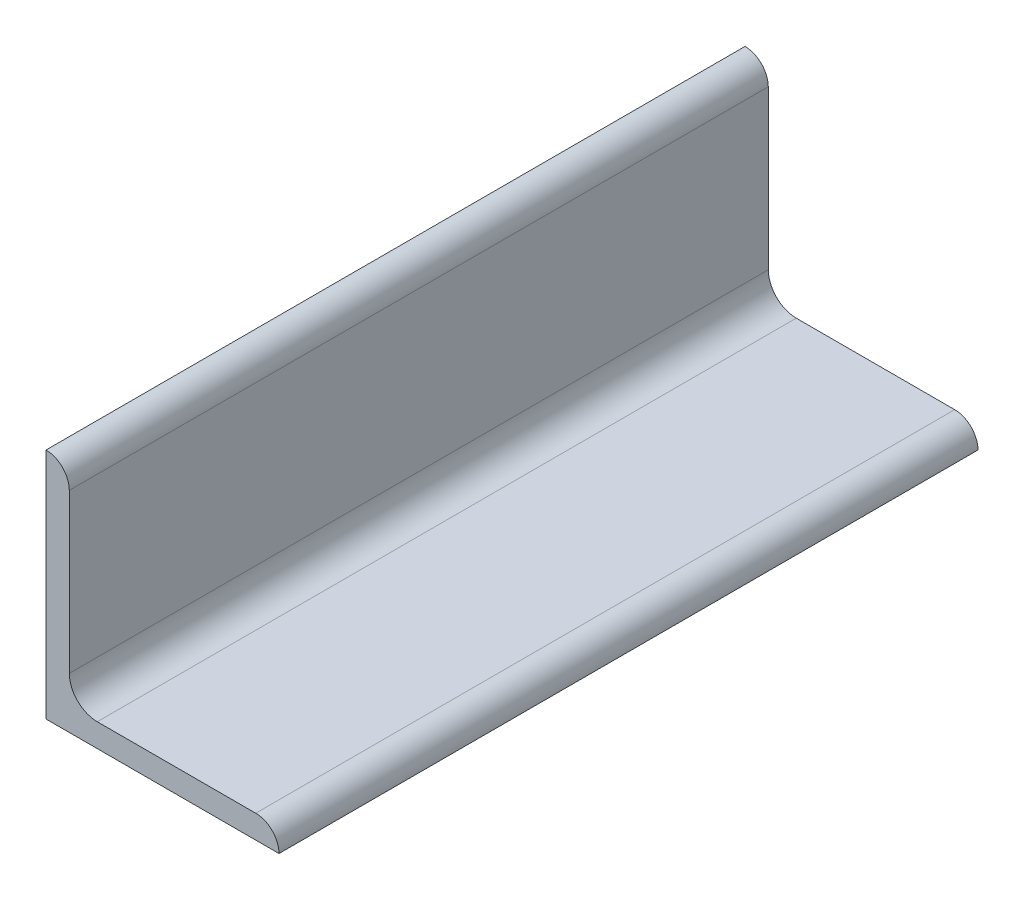
SolidWorks part; units mm, degrees
ref_plane "Plane1" through (0, 0, 0) normal (0, 0, 1) x (1, 0, 0)
ref_plane "Plane2" through (0, 0, 0) normal (0, 1, 0) x (1, 0, 0)
ref_plane "Plane3" through (0, 0, 0) normal (1, 0, 0) x (0, 0, -1)
sketch "Sketch1" plane through (0, 0, 0) normal (0, 0, 1) x (1, 0, 0)
  line L0 (0, 100) -> (0, 0)
  line L1 (0, 100) -> (9.525, 100) construction
  line L2 (10, 100) -> (10, 22)
  line L3 (22, 10) -> (100, 10)
  line L4 (100, 9.525) -> (100, 0) construction
  line L5 (100, 0) -> (0, 0)
  line L6 (100, 10) -> (100, 0)
  line L7 (0, 100) -> (10, 100)
  arc A2 (22, 10) -> (10, 22) centre (22, 22) cw
  dimension "Radius_1" = 12
  dimension "V_leg" = 100
  dimension "H_leg" = 100
extrude "BaseSteelAngle" add sketch "Sketch1" along normal mid plane 300
fillet "ToeFillet" radius 10 2 edges at (100, 10, 0) (10, 100, 0)
